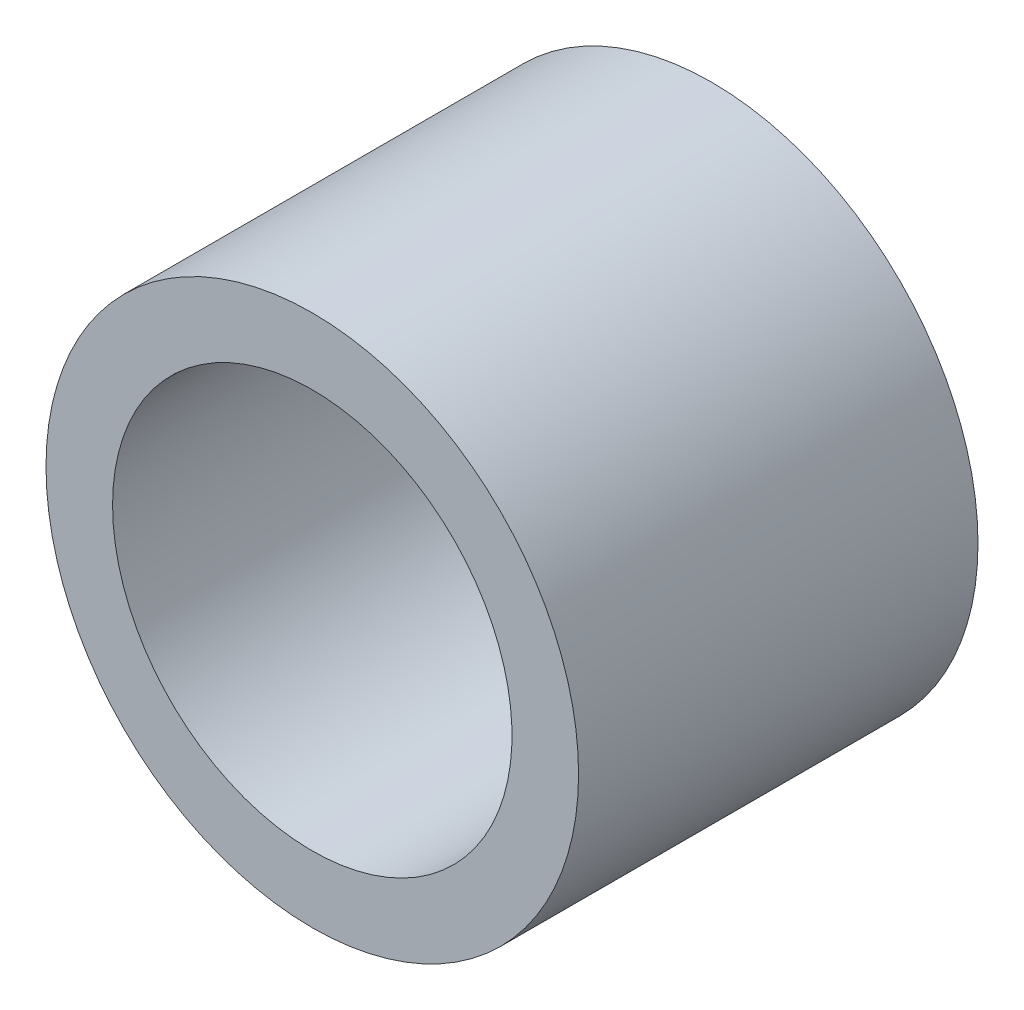
SolidWorks part; units mm, degrees
material "Tin Bearing Bronze"
ref_plane "Front Plane" through (0, 0, 0) normal (0, 0, 1) x (1, 0, 0)
ref_plane "Top Plane" through (0, 0, 0) normal (0, 1, 0) x (1, 0, 0)
ref_plane "Right Plane" through (0, 0, 0) normal (1, 0, 0) x (0, 0, -1)
sketch "Sketch1" plane through (0, 0, 0) normal (0, 0, 1) x (1, 0, 0)
  circle A0 centre (0, 0) radius 4.7625
  circle A1 centre (0, 0) radius 6.35
  dimension "D1" = 9.525
  dimension "D2" = 12.7
extrude "Boss-Extrude1" add sketch "Sketch1" along normal blind 9.525
equation "\"dovetail-angle\"= 55"
equation "\"dovetail-stock-width\"= 5"
equation "\"dovetail-stock-height\"= 1.25"
equation "\"dovetail-depth\"= 0.5 * \"dovetail-stock-height\""
equation "\"dovetail-throat-width\"= \"dovetail-stock-width\" - (2 * \"dovetail-depth\")"
equation "\"delta-x\"= 6"
equation "\"delta-y\"= 3"
equation "\"delta-z\"= 2.5"
equation "\"gib-thickness\"= 0.25"
equation "\"x-slide-length\"= \"dovetail-stock-width\" + \"delta-x\""
equation "\"y-slide-length\"= \"dovetail-stock-width\" + \"delta-y\""
equation "\"dog-point-diam\"= .149"
equation "\"dog-point-length\"= .067"
equation "\"dovetail-double-height\"= 2 * \"dovetail-depth\" + 0.5"
equation "\"acme-major-diam\"= .5"
equation "\"acme-pitch-diam\"= 0.45"
equation "\"acme-minor-diam\"= 0.4"
equation "\"x-screw-length\"= \"x-slide-length\" + \"screw-add-length\""
equation "\"y-screw-length\"= \"y-slide-length\" + \"screw-add-length\""
equation "\"acme-nut-od\"= 1.47"
equation "\"acme-nut-length\"= 1"
equation "\"acme-nut-trim-height\"= .75"
equation "\"screw-bearing-od\"= 0.5"
equation "\"screw-bearing-length\"= .375"
equation "\"end-plate-thickness\"= \"screw-bearing-length\""
equation "\"screw-bearing-id\"= .375"
equation "\"D1@Sketch1\"=\"screw-bearing-id\""
equation "\"D2@Sketch1\"=\"screw-bearing-od\""
equation "\"D1@Boss-Extrude1\"=\"screw-bearing-length\""
